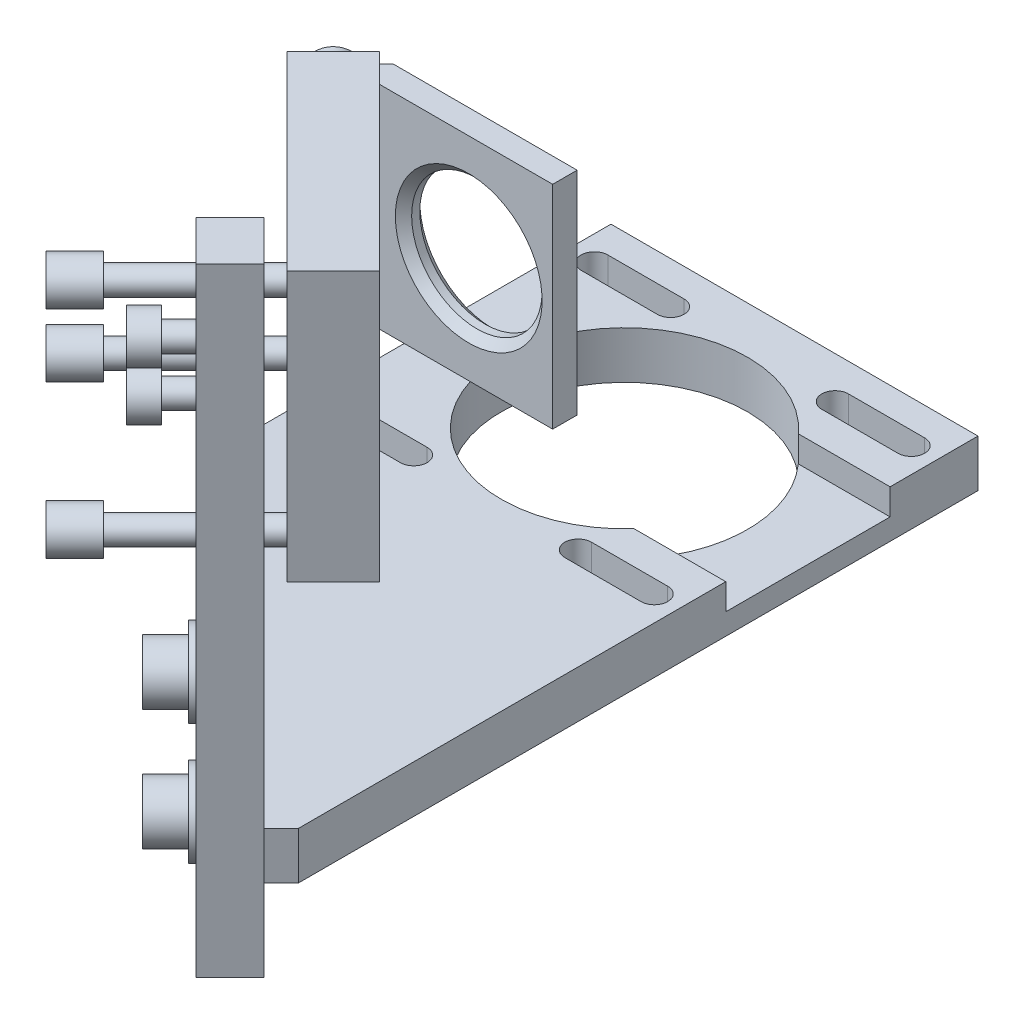
SolidWorks part; units mm, degrees
ref_plane "laser X plane" through (0, 0, 0) normal (0, 0, 1) x (1, 0, 0)
ref_plane "laser Z plane" through (0, 0, 0) normal (0, 1, 0) x (1, 0, 0)
ref_plane "laser Y plane" through (0, 0, 0) normal (1, 0, 0) x (0, 0, -1)
ref_plane "Plane1" through (0, -32.5, 0) normal (0, 1, 0) x (1, 0, 0)
sketch "Sketch1" plane through (0, -32.5, 0) normal (0, 1, 0) x (1, 0, 0)
  line L0 (0, 0) -> (56.0742, 0) construction
  line L1 (0, 0) -> (0, 59.4556) construction
  line L2 (1.05, 5.8) -> (10.05, 5.8) construction
  line L3 (-34.9, 15) -> (15, 15)
  line L4 (-34.9, 15) -> (-34.9, -34.9)
  line L5 (-34.9, -34.9) -> (15, -34.9)
  line L6 (15, 15) -> (15, -34.9)
  line L7 (1.05, 8.3) -> (10.05, 8.3)
  line L8 (1.05, 3.3) -> (10.05, 3.3)
  line L9 (-9.95, 15) -> (-9.95, -34.9) construction
  line L10 (-34.9, -9.95) -> (15, -9.95) construction
  line L11 (-20.95, 5.8) -> (-29.95, 5.8) construction
  line L12 (-20.95, 8.3) -> (-29.95, 8.3)
  line L13 (-20.95, 3.3) -> (-29.95, 3.3)
  line L14 (-20.95, -25.7) -> (-29.95, -25.7) construction
  line L15 (-20.95, -28.2) -> (-29.95, -28.2)
  line L16 (-20.95, -23.2) -> (-29.95, -23.2)
  line L17 (1.05, -25.7) -> (10.05, -25.7) construction
  line L18 (1.05, -28.2) -> (10.05, -28.2)
  line L19 (1.05, -23.2) -> (10.05, -23.2)
  arc A0 (1.05, 8.3) -> (1.05, 3.3) centre (1.05, 5.8) ccw
  arc A1 (10.05, 3.3) -> (10.05, 8.3) centre (10.05, 5.8) ccw
  arc A2 (-20.95, 8.3) -> (-20.95, 3.3) centre (-20.95, 5.8) cw
  arc A3 (-29.95, 3.3) -> (-29.95, 8.3) centre (-29.95, 5.8) cw
  arc A4 (-20.95, -28.2) -> (-20.95, -23.2) centre (-20.95, -25.7) ccw
  arc A5 (-29.95, -23.2) -> (-29.95, -28.2) centre (-29.95, -25.7) ccw
  arc A6 (1.05, -28.2) -> (1.05, -23.2) centre (1.05, -25.7) cw
  arc A7 (10.05, -23.2) -> (10.05, -28.2) centre (10.05, -25.7) cw
  point P10 (5.55, 5.8)
  point P21 (-25.45, 5.8)
  point P28 (-25.45, -25.7)
  point P35 (5.55, -25.7)
  dimension "D7" = 22
  dimension "D1" = 49.9
  dimension "D2" = 49.9
  dimension "D3" = 15
  dimension "D4" = 15
  dimension "D5" = 5
  dimension "D6" = 9
  dimension "D8" = 26.5
  dimension "D9" = 6.7
  dimension "D10" = 31.5
  dimension "D11" = 31
extrude "Boss-Extrude1" add sketch "Sketch1" against normal blind 6
ref_axis "Axis1" through (0, 50, 0) along (0, -1, 0)
ref_plane "mirror plane" through (0, 0, 0) normal (0.7071, 0, -0.7071) x (0, -1, 0)
ref_axis "incoming laser beam" through (0, 0, -80.9) along (0, 0, 1)
ref_axis "outgoing laser beam" through (2.1578, 0, 0) along (1, 0, 0)
ref_plane "Plane3" through (-6.364, 0, 6.364) normal (0.7071, 0, -0.7071) x (0, -1, 0)
sketch "Sketch2" plane through (-6.364, 0, 6.364) normal (0.7071, 0, -0.7071) x (0, -1, 0)
  line L0 (-50, 0) -> (50, 0) construction
  line L1 (0, 50) -> (0, -50) construction
  line L2 (-5.5453, -9.5) -> (-17.25, -9.5)
  line L3 (-17.25, -9.5) -> (-17.25, -16.5)
  line L4 (-17.25, -16.5) -> (32.5, -16.5)
  line L5 (32.5, -16.5) -> (32.5, 16.5)
  line L6 (32.5, 16.5) -> (8.9, 16.5)
  line L7 (8.9, 16.5) -> (8.9, 6.4645)
  line L8 (32.5, 35.2846) -> (32.5, 0) construction
  line L9 (0, 0) -> (21.3656, 0) construction
  arc A0 (-5.5453, -9.5) -> (8.9, 6.4645) centre (0, 0) ccw
  dimension "D1" = 22
  dimension "D2" = 33
  dimension "D3" = 7
  dimension "D4" = 49.75
  dimension "D5" = 23.6
extrude "Boss-Extrude2" add sketch "Sketch2" against normal blind 5.9
sketch "Sketch3" plane through (-10.5359, 0, 10.5359) normal (-0.7071, 0, 0.7071) x (0.7071, 0, 0.7071)
  line L0 (0, 0) -> (37.2247, 0) construction
  line L1 (0, 0) -> (0, 17.5234) construction
  line L2 (13.25, 13.25) -> (13.25, -13.25) construction
  line L3 (13.25, -13.25) -> (-13.25, -13.25) construction
  arc A0 (-6.4645, -8.9) -> (9.5, 5.5453) centre (0, 0) ccw construction
  arc A1 (-6.4645, -8.9) -> (9.5, 5.5453) centre (0, 0) ccw construction
  circle A2 centre (13.25, 13.25) radius 1.5
  circle A3 centre (13.25, -13.25) radius 1.5
  circle A4 centre (-13.25, -13.25) radius 1.5
  dimension "D1" = 3
  dimension "D2" = 26.5
  dimension "D3" = 26.5
extrude "Boss-Extrude3" add sketch "Sketch3" along normal blind 13 and the other way up to surface (14.9 mm away) other way up to plane "mirror plane"
sketch "Sketch4" plane through (-19.7283, 0, 19.7283) normal (-0.7071, 0, 0.7071) x (0.7071, 0, 0.7071)
  circle A0 centre (13.25, 13.25) radius 2.5
  circle A1 centre (13.25, -13.25) radius 2.5
  circle A2 centre (-13.25, -13.25) radius 2.5
  dimension "D1" = 5
extrude "Boss-Extrude4" add sketch "Sketch4" against normal blind 5
sketch "Sketch5" plane through (-10.5359, 0, 10.5359) normal (-0.7071, 0, 0.7071) x (0.7071, 0, 0.7071)
  line L0 (13.25, 13.25) -> (13.25, -13.25) construction
  line L1 (13.25, -13.25) -> (-13.25, -13.25) construction
  circle A0 centre (-7.25, -13.25) radius 1.5
  circle A1 centre (13.25, 7.25) radius 1.5
  dimension "D1" = 3
  dimension "D2" = 6
  dimension "D3" = 6
extrude "Boss-Extrude5" add sketch "Sketch5" along normal blind 3
sketch "Sketch6" plane through (-12.6572, 0, 12.6572) normal (-0.7071, 0, 0.7071) x (0.7071, 0, 0.7071)
  circle A0 centre (13.25, 7.25) radius 2.75
  circle A1 centre (-7.25, -13.25) radius 2.75
  dimension "D1" = 5.5
extrude "Boss-Extrude6" add sketch "Sketch6" along normal blind 0.5
sketch "Sketch7" plane through (-13.0108, 0, 13.0108) normal (-0.7071, 0, 0.7071) x (0.7071, 0, 0.7071)
  line L1 (-6.2214, -12.2374) -> (-7.6126, -11.8529)
  line L2 (-7.6126, -11.8529) -> (-8.6412, -12.8655)
  line L3 (13.7871, 5.9103) -> (14.6788, 7.0453)
  line L4 (14.6788, 7.0453) -> (14.1417, 8.385)
  line L5 (14.1417, 8.385) -> (12.7129, 8.5897)
  line L6 (12.7129, 8.5897) -> (11.8212, 7.4547)
  line L7 (11.8212, 7.4547) -> (12.3583, 6.115)
  line L8 (12.3583, 6.115) -> (13.7871, 5.9103)
  line L9 (-8.6412, -12.8655) -> (-8.2786, -14.2626)
  line L10 (-8.2786, -14.2626) -> (-6.8874, -14.6471)
  line L11 (-6.8874, -14.6471) -> (-5.8588, -13.6345)
  line L12 (-5.8588, -13.6345) -> (-6.2214, -12.2374)
  circle A0 centre (-7.25, -13.25) radius 2.75 construction
  circle A1 centre (13.25, 7.25) radius 2.75 construction
  circle A2 centre (-7.25, -13.25) radius 2.75
  circle A3 centre (13.25, 7.25) radius 2.75
  circle A4 centre (13.25, 7.25) radius 1.25 construction
  circle A5 centre (-7.25, -13.25) radius 1.25 construction
  dimension "D1" = 2.5
extrude "Boss-Extrude7" add sketch "Sketch7" along normal blind 2.5
sketch "Sketch8" plane through (0, 0, 0) normal (0.7071, 0, -0.7071) x (0, -1, 0)
  line L0 (0, 0) -> (0, 38.3007) construction
  line L1 (0, 0) -> (-35.7157, 0) construction
  line L3 (16.5, 16.5) -> (-16.5, 16.5)
  line L4 (16.5, 16.5) -> (16.5, -16.5)
  line L5 (16.5, -16.5) -> (-16.5, -16.5)
  line L6 (-16.5, 16.5) -> (-16.5, -16.5)
  line L7 (16.5, 16.5) -> (-16.5, -16.5) construction
  line L8 (16.5, -16.5) -> (-16.5, 16.5) construction
  circle A0 centre (0, 0) radius 8.675
  dimension "D2" = 17.35
  dimension "D1" = 33
extrude "Boss-Extrude8" add sketch "Sketch8" along normal blind 1
sketch "Sketch9" plane through (0, 0, 0) normal (-0.7071, 0, 0.7071) x (0.7071, 0, 0.7071)
  line L4 (16.5, 16.5) -> (-16.5, 16.5)
  line L5 (-16.5, 16.5) -> (-16.5, -16.5)
  line L6 (-16.5, -16.5) -> (16.5, -16.5)
  line L7 (16.5, -16.5) -> (16.5, 16.5)
  line L8 (16.5, 16.5) -> (-16.5, 16.5)
  line L9 (-16.5, 16.5) -> (-16.5, -16.5)
  line L10 (-16.5, -16.5) -> (16.5, -16.5)
  line L11 (16.5, -16.5) -> (16.5, 16.5)
  circle A0 centre (0, 0) radius 10.15
  dimension "D2" = 20.3
  dimension "D1" = 0
extrude "Boss-Extrude9" add sketch "Sketch9" along normal blind 7
sketch "Sketch10" plane through (0, 0, 0) normal (-0.7071, 0, 0.7071) x (0.7071, 0, 0.7071)
  circle A0 centre (0, 0) radius 10
  dimension "D1" = 20
extrude "Boss-Extrude10" add sketch "Sketch10" along normal blind 2
sketch "Sketch11" plane through (-1.4142, 0, 1.4142) normal (-0.7071, 0, 0.7071) x (0.7071, 0, 0.7071)
  circle A0 centre (0, 0) radius 10.15 construction
  circle A1 centre (0, 0) radius 10.15
  circle A2 centre (0, 0) radius 6
  dimension "D1" = 12
extrude "Boss-Extrude11" add sketch "Sketch11" along normal blind 3
sketch "Sketch12" plane through (0, -38.5, 0) normal (0, -1, 0) x (1, 0, 0)
  line L0 (1.1314, 22.2032) -> (5.3033, 18.0312) construction
  line L1 (5.3033, 18.0312) -> (-18.0312, -5.3033) construction
  line L2 (-22.2032, -1.1314) -> (-19.699, -3.6355) construction
  line L3 (1.1314, 22.2032) -> (-22.2032, -1.1314) construction
  line L4 (1.1314, 22.2032) -> (5.3033, 18.0312) construction
  line L5 (5.3033, 18.0312) -> (-18.0312, -5.3033) construction
  line L6 (-22.2032, -1.1314) -> (-18.0312, -5.3033) construction
  line L7 (1.1314, 22.2032) -> (-22.2032, -1.1314) construction
  line L8 (-20.1172, -3.2173) -> (3.2173, 20.1172) construction
  line L9 (-10.5359, 10.5359) -> (-6.364, 6.364) construction
  circle A0 centre (-15.3442, 1.5556) radius 2
  circle A1 centre (-1.5556, 15.3442) radius 2
  dimension "D1" = 19.5
  dimension "D2" = 4
extrude "Cut-Extrude1" cut sketch "Sketch12" against normal blind 13
sketch "Sketch13" plane through (0, -38.5, 0) normal (0, -1, 0) x (1, 0, 0)
  circle A0 centre (-15.3442, 1.5556) radius 4
  circle A1 centre (-1.5556, 15.3442) radius 4
  dimension "D1" = 8
extrude "Cut-Extrude2" cut sketch "Sketch13" against normal blind 4
sketch "Sketch14" plane through (0, -34.5, 0) normal (0, -1, 0) x (1, 0, 0)
  circle A0 centre (-15.3442, 1.5556) radius 3.5
  circle A1 centre (-1.5556, 15.3442) radius 3.5
  dimension "D1" = 7
extrude "Boss-Extrude12" add sketch "Sketch14" along normal blind 1
sketch "Sketch15" plane through (0, -35.5, 0) normal (0, -1, 0) x (1, 0, 0)
  line L1 (-14.2979, 2.936) -> (-16.0165, 3.1519)
  line L2 (-16.0165, 3.1519) -> (-17.0628, 1.7716)
  line L3 (-17.0628, 1.7716) -> (-16.3905, 0.1753)
  line L4 (-16.3905, 0.1753) -> (-14.672, -0.0406)
  line L5 (-14.672, -0.0406) -> (-13.6257, 1.3397)
  line L6 (-13.6257, 1.3397) -> (-14.2979, 2.936)
  line L7 (-2.6654, 16.674) -> (-3.2622, 15.048)
  line L8 (-3.2622, 15.048) -> (-2.1524, 13.7182)
  line L9 (-2.1524, 13.7182) -> (-0.4458, 14.0144)
  line L10 (-0.4458, 14.0144) -> (0.1509, 15.6404)
  line L11 (0.1509, 15.6404) -> (-0.9589, 16.9702)
  line L12 (-0.9589, 16.9702) -> (-2.6654, 16.674)
  circle A0 centre (-1.5556, 15.3442) radius 3.5 construction
  circle A1 centre (-15.3442, 1.5556) radius 3.5 construction
  circle A2 centre (-1.5556, 15.3442) radius 3.5
  circle A3 centre (-15.3442, 1.5556) radius 3.5
  circle A4 centre (-15.3442, 1.5556) radius 1.5 construction
  circle A5 centre (-1.5556, 15.3442) radius 1.5 construction
  dimension "D1" = 3
extrude "Boss-Extrude13" add sketch "Sketch15" along normal blind 3
sketch "Sketch16" plane through (0, 0, 0) normal (0, 1, 0) x (1, 0, 0)
  line L0 (-10.9602, 12.3744) -> (-16.617, 6.7175) construction
  line L1 (-10.9602, 12.3744) -> (-16.2635, 7.0711)
  line L2 (-16.2635, 7.0711) -> (-18.3848, 9.1924)
  line L3 (-18.3848, 9.1924) -> (-12.2028, 15.3744)
  line L4 (-12.2028, 15.3744) -> (10.2898, 15.3744)
  line L5 (10.2898, 15.3744) -> (10.2898, 12.3744)
  line L6 (10.2898, 12.3744) -> (-10.9602, 12.3744)
  dimension "D1" = 7.5
  dimension "D2" = 3
  dimension "D3" = 3
  dimension "D4" = 21.25
extrude "Boss-Extrude14" add sketch "Sketch16" along normal mid plane 26
sketch "Sketch17" plane through (0, 0, -15.3744) normal (0, 0, -1) x (-1, 0, 0)
  line L0 (0, 0) -> (0, -20.2812) construction
  circle A0 centre (0, 0) radius 8
  dimension "D1" = 16
extrude "Cut-Extrude3" cut sketch "Sketch17" against normal blind 3
chamfer "Chamfer1" distance 1 angle 45 2 edges at (-8, 0, -12.3744) (-8, 0, -15.3744)
sketch "Sketch18" plane through (-13.7886, 0, -13.7886) normal (-0.7071, 0, -0.7071) x (-0.7071, 0, 0.7071)
  line L0 (-1, 16.5) -> (7, 16.5) construction
  line L1 (-1, 16.5) -> (7, 16.5) construction
  line L2 (3, 16.5) -> (3, -14.02) construction
  line L3 (-2.2426, 13) -> (-2.2426, -13) construction
  line L4 (-2.2426, 13) -> (-2.2426, -13) construction
  line L5 (-2.2426, 0) -> (5.8439, 0) construction
  circle A0 centre (3, 10) radius 2.75
  circle A1 centre (3, -10) radius 2.75
  dimension "D1" = 5.5
  dimension "D2" = 20
extrude "Boss-Extrude15" add sketch "Sketch18" along normal blind 0.5
sketch "Sketch19" plane through (-14.1421, 0, -14.1421) normal (-0.7071, 0, -0.7071) x (-0.7071, 0, 0.7071)
  line L1 (1.8482, 9.1301) -> (3.1775, 8.5676)
  line L2 (3.1775, 8.5676) -> (4.3292, 9.4375)
  line L3 (4.3292, 9.4375) -> (4.1518, 10.8699)
  line L4 (4.1518, 10.8699) -> (2.8225, 11.4324)
  line L5 (2.8225, 11.4324) -> (1.6708, 10.5625)
  line L6 (1.6708, 10.5625) -> (1.8482, 9.1301)
  line L7 (3.6669, -11.2801) -> (4.442, -10.0625)
  line L8 (4.442, -10.0625) -> (3.7751, -8.7824)
  line L9 (3.7751, -8.7824) -> (2.3331, -8.7199)
  line L10 (2.3331, -8.7199) -> (1.558, -9.9375)
  line L11 (1.558, -9.9375) -> (2.2249, -11.2176)
  line L12 (2.2249, -11.2176) -> (3.6669, -11.2801)
  circle A0 centre (3, -10) radius 2.75 construction
  circle A1 centre (3, 10) radius 2.75 construction
  circle A2 centre (3, -10) radius 2.75
  circle A3 centre (3, 10) radius 2.75
  circle A4 centre (3, 10) radius 1.25 construction
  circle A5 centre (3, -10) radius 1.25 construction
  dimension "D1" = 2.5
extrude "Boss-Extrude16" add sketch "Sketch19" along normal blind 2.5
sketch "Sketch20" plane through (0, -16.5, 0) normal (0, -1, 0) x (1, 0, 0)
  line L1 (32.8956, 59.0573) -> (-65.028, 59.0573)
  line L2 (32.8956, 59.0573) -> (32.8956, -51.1154)
  line L3 (32.8956, -51.1154) -> (-65.028, -51.1154)
  line L4 (-65.028, 59.0573) -> (-65.028, -51.1154)
extrude "Cut-Extrude4" cut sketch "Sketch20" along normal through all
sketch "Sketch21" plane through (0, -16.5, 0) normal (0, -1, 0) x (1, 0, 0)
  line L4 (-22.2032, -1.1314) -> (-18.0312, -5.3033)
  line L5 (-18.0312, -5.3033) -> (5.3033, 18.0312)
  line L6 (5.3033, 18.0312) -> (1.1314, 22.2032)
  line L7 (1.1314, 22.2032) -> (-22.2032, -1.1314)
  line L8 (-22.2032, -1.1314) -> (-18.0312, -5.3033)
  line L9 (-18.0312, -5.3033) -> (5.3033, 18.0312)
  line L10 (5.3033, 18.0312) -> (1.1314, 22.2032)
  line L11 (1.1314, 22.2032) -> (-22.2032, -1.1314)
  dimension "D1" = 0
extrude "Boss-Extrude17" add sketch "Sketch21" along normal blind 42
sketch "Sketch22" plane through (-10.5359, 0, 10.5359) normal (-0.7071, 0, 0.7071) x (0.7071, 0, 0.7071)
  line L0 (0, 0) -> (0, -78.1981) construction
  line L1 (-11.4427, -49.65) -> (10.5, -49.65) construction
  line L2 (10.5, -54.15) -> (10.5, -45.15) construction
  line L3 (8, -54.15) -> (8, -45.15)
  line L4 (13, -54.15) -> (13, -45.15)
  line L5 (-10.5, -54.15) -> (-10.5, -45.15) construction
  line L6 (-8, -54.15) -> (-8, -45.15)
  line L7 (-13, -54.15) -> (-13, -45.15)
  line L8 (16.5, -58.5) -> (-16.5, -58.5) construction
  arc A0 (8, -54.15) -> (13, -54.15) centre (10.5, -54.15) ccw
  arc A1 (13, -45.15) -> (8, -45.15) centre (10.5, -45.15) ccw
  arc A2 (-8, -54.15) -> (-13, -54.15) centre (-10.5, -54.15) cw
  arc A3 (-13, -45.15) -> (-8, -45.15) centre (-10.5, -45.15) cw
  point P7 (10.5, -49.65)
  point P14 (-10.5, -49.65)
  dimension "D4" = 1.85
  dimension "D1" = 5
  dimension "D2" = 14
  dimension "D3" = 21
extrude "Cut-Extrude5" cut sketch "Sketch22" against normal through all
ref_plane "Plane4" through (0, -41.75, 0) normal (0, -1, 0) x (-1, 0, 0)
sketch "Sketch23" plane through (0, -41.75, 0) normal (0, -1, 0) x (-1, 0, 0)
  line L0 (18.0312, 5.3033) -> (-5.3033, -18.0312) construction
  line L1 (36.6561, 23.9282) -> (-6.2225, -18.9505)
  line L2 (0, 0) -> (-28.4035, 0) construction
  line L3 (0, 0) -> (0, 57.7643) construction
  line L4 (-5.3033, -18.0312) -> (-1.1314, -22.2032) construction
  line L5 (-5.3033, -18.0312) -> (-1.1314, -22.2032) construction
  line L6 (-6.2225, -18.9505) -> (-8.3439, -16.8291)
  line L7 (-8.3439, -16.8291) -> (-8.3439, 66.4688)
  line L8 (-8.3439, 66.4688) -> (36.6561, 66.4688)
  line L9 (36.6561, 66.4688) -> (36.6561, 23.9282)
  line L10 (14.1561, 66.4688) -> (14.1561, 54.1076) construction
  line L11 (33.5764, 61.3688) -> (24.2359, 61.3688) construction
  line L12 (33.5764, 59.7322) -> (24.2359, 59.7322)
  line L13 (33.5764, 63.0053) -> (24.2359, 63.0053)
  line L14 (14.1561, 45.6188) -> (24.2359, 45.6188) construction
  line L15 (-5.2641, 61.3688) -> (4.0764, 61.3688) construction
  line L16 (-5.2641, 59.7322) -> (4.0764, 59.7322)
  line L17 (-5.2641, 63.0053) -> (4.0764, 63.0053)
  line L18 (33.5764, 29.8688) -> (24.2359, 29.8688) construction
  line L19 (33.5764, 31.5053) -> (24.2359, 31.5053)
  line L20 (33.5764, 28.2322) -> (24.2359, 28.2322)
  line L21 (-5.2641, 29.8688) -> (4.0764, 29.8688) construction
  line L22 (-5.2641, 31.5053) -> (4.0764, 31.5053)
  line L23 (-5.2641, 28.2322) -> (4.0764, 28.2322)
  circle A0 centre (14.1561, 45.6188) radius 15.1
  arc A1 (33.5764, 59.7322) -> (33.5764, 63.0053) centre (33.5764, 61.3688) ccw
  arc A2 (24.2359, 63.0053) -> (24.2359, 59.7322) centre (24.2359, 61.3688) ccw
  arc A3 (-5.2641, 59.7322) -> (-5.2641, 63.0053) centre (-5.2641, 61.3688) cw
  arc A4 (4.0764, 63.0053) -> (4.0764, 59.7322) centre (4.0764, 61.3688) cw
  arc A5 (33.5764, 31.5053) -> (33.5764, 28.2322) centre (33.5764, 29.8688) cw
  arc A6 (24.2359, 28.2322) -> (24.2359, 31.5053) centre (24.2359, 29.8688) cw
  arc A7 (-5.2641, 31.5053) -> (-5.2641, 28.2322) centre (-5.2641, 29.8688) ccw
  arc A8 (4.0764, 28.2322) -> (4.0764, 31.5053) centre (4.0764, 29.8688) ccw
  point P17 (28.9061, 61.3688)
  point P26 (-0.5939, 61.3688)
  point P33 (28.9061, 29.8688)
  point P40 (-0.5939, 29.8688)
  dimension "D5" = 30.2
  dimension "D6" = 5.75
  dimension "D1" = 1.3
  dimension "D2" = 3
  dimension "D3" = 84.5
  dimension "D4" = 45
  dimension "D7" = 3.2731
  dimension "D8" = 12.6136
  dimension "D9" = 31.5
  dimension "D10" = 29.5
extrude "Boss-Extrude18" add sketch "Sketch23" along normal blind 5.8
sketch "Sketch24" plane through (0, -41.75, 0) normal (0, 1, 0) x (1, 0, 0)
  line L0 (8.3439, 66.4688) -> (8.3439, -16.8291) construction
  line L1 (8.3439, 55.6938) -> (8.3439, 35.5438)
  line L2 (-14.1561, 45.6188) -> (36.7014, 45.6188) construction
  line L3 (-2.9087, 35.5438) -> (8.3439, 35.5438)
  line L4 (-2.9087, 55.6938) -> (8.3439, 55.6938)
  circle A0 centre (-14.1561, 45.6188) radius 15.1 construction
  arc A1 (-2.9087, 35.5438) -> (-2.9087, 55.6938) centre (-14.1561, 45.6188) ccw
  dimension "D1" = 20.15
extrude "Cut-Extrude6" cut sketch "Sketch24" against normal blind 3.2
sketch "Sketch25" plane through (-10.5359, 0, 10.5359) normal (-0.7071, 0, 0.7071) x (0.7071, 0, 0.7071)
  line L0 (-10.5, -42.65) -> (-10.5, -45.15) construction
  line L1 (-10.5, -45.15) -> (10.5, -45.15) construction
  line L2 (0, -45.15) -> (0, -51.89) construction
  arc A0 (-8, -45.15) -> (-13, -45.15) centre (-10.5, -45.15) ccw construction
  circle A1 centre (-10.5, -45.15) radius 4.5
  circle A2 centre (10.5, -45.15) radius 4.5
  dimension "D1" = 9
extrude "Boss-Extrude19" add sketch "Sketch25" along normal blind 0.65
sketch "Sketch26" plane through (-10.9955, 0, 10.9955) normal (-0.7071, 0, 0.7071) x (0.7071, 0, 0.7071)
  circle A0 centre (-10.5, -45.15) radius 3.25
  circle A1 centre (10.5, -45.15) radius 3.25
  dimension "D1" = 6.5
extrude "Boss-Extrude20" add sketch "Sketch26" along normal blind 1
sketch "Sketch27" plane through (-11.7026, 0, 11.7026) normal (-0.7071, 0, 0.7071) x (0.7071, 0, 0.7071)
  line L1 (11.5601, -46.5197) -> (12.2163, -44.9168)
  line L2 (12.2163, -44.9168) -> (11.1562, -43.5471)
  line L3 (-8.9107, -45.8385) -> (-9.1091, -44.1179)
  line L4 (-9.1091, -44.1179) -> (-10.6984, -43.4294)
  line L5 (-10.6984, -43.4294) -> (-12.0893, -44.4615)
  line L6 (-12.0893, -44.4615) -> (-11.8909, -46.1821)
  line L7 (-11.8909, -46.1821) -> (-10.3016, -46.8706)
  line L8 (-10.3016, -46.8706) -> (-8.9107, -45.8385)
  line L9 (11.1562, -43.5471) -> (9.4399, -43.7803)
  line L10 (9.4399, -43.7803) -> (8.7837, -45.3832)
  line L11 (8.7837, -45.3832) -> (9.8438, -46.7529)
  line L12 (9.8438, -46.7529) -> (11.5601, -46.5197)
  circle A0 centre (10.5, -45.15) radius 3.25 construction
  circle A1 centre (-10.5, -45.15) radius 3.25 construction
  circle A2 centre (10.5, -45.15) radius 3.25
  circle A3 centre (-10.5, -45.15) radius 3.25
  circle A4 centre (-10.5, -45.15) radius 1.5 construction
  circle A5 centre (10.5, -45.15) radius 1.5 construction
  dimension "D1" = 3
extrude "Boss-Extrude21" add sketch "Sketch27" along normal blind 3
